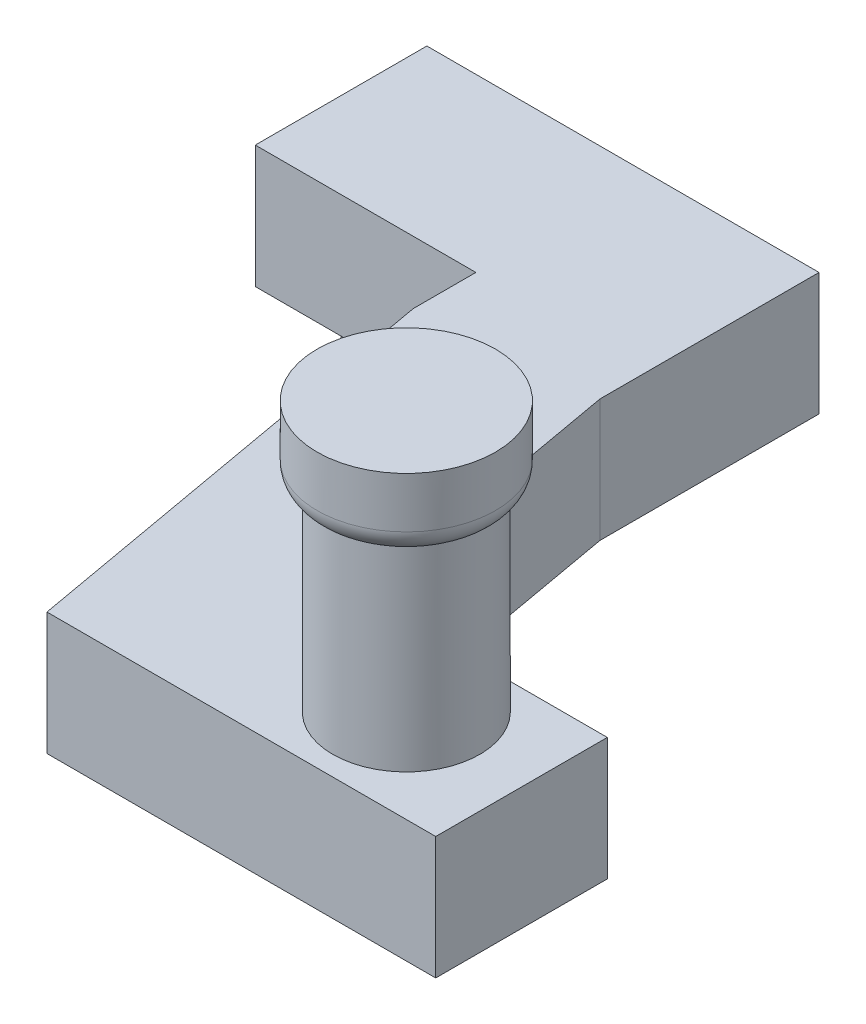
SolidWorks part; units mm, degrees
ref_plane "Front Plane" through (0, 0, 0) normal (0, 0, 1) x (1, 0, 0)
ref_plane "Top Plane" through (0, 0, 0) normal (0, 1, 0) x (1, 0, 0)
ref_plane "Right Plane" through (0, 0, 0) normal (1, 0, 0) x (0, 0, -1)
sketch "Sketch1" plane through (0, 0, 0) normal (0, 1, 0) x (1, 0, 0)
  line L0 (0, 0) -> (8, 0)
  line L1 (8, 0) -> (8, -4.4673)
  line L2 (8, -4.4673) -> (9.0546, -10.3739)
  line L3 (9.0546, -10.3739) -> (14.0546, -10.3739)
  line L4 (0, -3.5) -> (4.5, -3.5)
  line L5 (4.5, -3.5) -> (4.5, -4.7773)
  line L6 (4.5, -4.7773) -> (6.1242, -13.8739)
  line L7 (6.1242, -13.8739) -> (14.0546, -13.8739)
  line L8 (14.0546, -10.3739) -> (14.0546, -13.8739)
  line L9 (0, 0) -> (0, -3.5)
  point P11 (11.1471, -10.6883)
  point P12 (8.7479, -10.4678)
  point P13 (9.0546, -10.3739)
  dimension "D1" = 8
  dimension "D2" = 6
  dimension "D4" = 5
  dimension "D5" = 3.5
extrude "Boss-Extrude1" add sketch "Sketch1" along normal blind 2.5
sketch "Sketch2" plane through (0, 2.5, 0) normal (0, 1, 0) x (1, 0, 0)
  line L0 (14.0546, -10.3739) -> (9.0546, -10.3739) construction
  line L1 (14.0546, -13.8739) -> (14.0546, -10.3739) construction
  circle A0 centre (11.5546, -11.9739) radius 1.5
  dimension "D1" = 1.6
  dimension "D2" = 2.5
extrude "Boss-Extrude2" add sketch "Sketch2" along normal blind 4
sketch "Sketch3" plane through (0, 6.5, 0) normal (0, 1, 0) x (1, 0, 0)
  circle A0 centre (11.5546, -11.9739) radius 1.82
extrude "Boss-Extrude3" add sketch "Sketch3" along normal blind 1.5
fillet "Fillet2" radius 0.5 1 edges at (11.5546, 6.5, 13.7939)
sketch "Sketch4" plane through (0, 0, 0) normal (0, -1, 0) x (-1, 0, 0)
  circle A0 centre (-1.718, -1.4929) radius 1.4
extrude "Boss-Extrude4" add sketch "Sketch4" along normal blind 3.5
sketch "Sketch5" plane through (0, -3.5, 0) normal (0, -1, 0) x (1, 0, 0)
  circle A0 centre (1.7071, 1.4764) radius 1.7
extrude "Boss-Extrude5" add sketch "Sketch5" along normal blind 1
fillet "Fillet3" radius 0.5 1 edges at (1.7071, -3.5, -0.2236)
